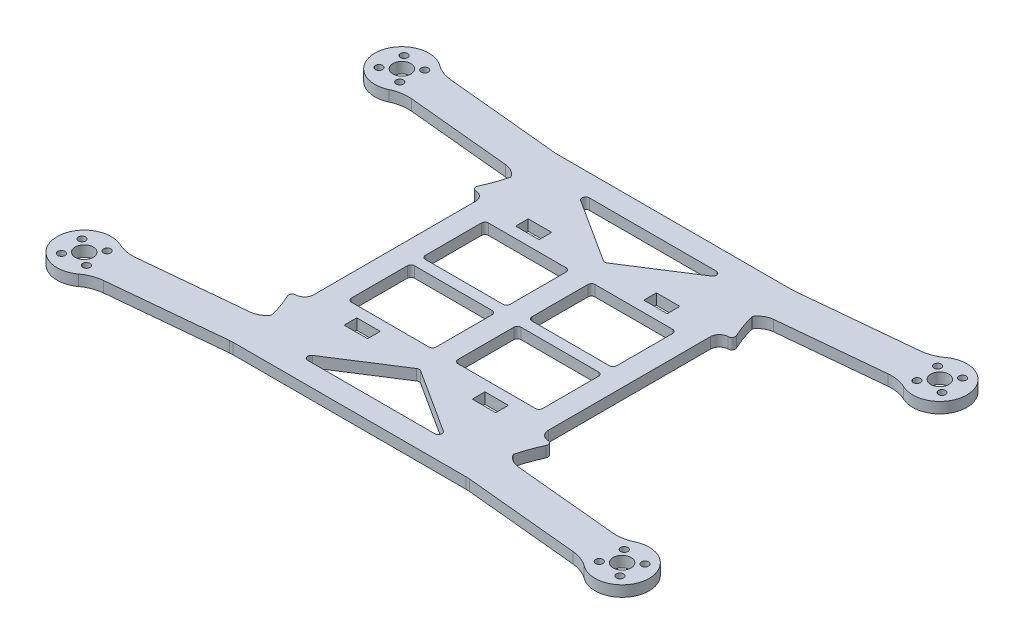
SolidWorks part; units mm, degrees
material "Custom PLA"
ref_plane "Front Plane" through (0, 0, 0) normal (0, 0, 1) x (1, 0, 0)
ref_plane "Top Plane" through (0, 0, 0) normal (0, 1, 0) x (1, 0, 0)
ref_plane "Right Plane" through (0, 0, 0) normal (1, 0, 0) x (0, 0, -1)
sketch "Sketch1" plane through (0, 0, 0) normal (0, 1, 0) x (1, 0, 0)
  line L0 (-101.3207, 0) -> (4964.7124, 0) construction
  line L1 (0, -101.3207) -> (0, 4964.7124) construction
  line L4 (33.2085, 45.046) -> (65.0466, 48.1117)
  line L5 (37.1258, 35.377) -> (66.0089, 38.1581)
  line L6 (0.5402, 25.8595) -> (18.1402, 37.1585)
  line L7 (4, 1.5) -> (25.5, 1.5)
  line L8 (3, 2.5) -> (3, 18)
  line L9 (4, 19) -> (25.5, 19)
  line L10 (26.5, 2.5) -> (26.5, 18)
  line L11 (14.5, 22) -> (21, 22)
  line L12 (14.5, 22) -> (14.5, 25.5)
  line L13 (14.5, 25.5) -> (21, 25.5)
  line L14 (21, 22) -> (21, 25.5)
  line L15 (17.6, 39) -> (-17.6, 39)
  line L16 (-18.1402, 37.1585) -> (-0.5402, 25.8595)
  line L17 (71.6376, 40.5277) -> (71.0277, 46.8624) construction
  line L18 (32.5, 22.4419) -> (32.5, -22.4419)
  line L30 (32.25, 45) -> (-32.25, 45)
  line L31 (-71.6376, 40.5277) -> (-71.0277, 46.8624) construction
  line L70 (-32.5, 22.4419) -> (-32.5, -22.4419)
  line L71 (-21, 22) -> (-21, 25.5)
  line L72 (-14.5, 25.5) -> (-21, 25.5)
  line L73 (-14.5, 22) -> (-14.5, 25.5)
  line L74 (-14.5, 22) -> (-21, 22)
  line L75 (-26.5, 2.5) -> (-26.5, 18)
  line L76 (-4, 19) -> (-25.5, 19)
  line L77 (-3, 2.5) -> (-3, 18)
  line L78 (-4, 1.5) -> (-25.5, 1.5)
  line L79 (-37.1258, 35.377) -> (-66.0089, 38.1581)
  line L80 (-33.2085, 45.046) -> (-65.0466, 48.1117)
  line L81 (-71.6376, -40.5277) -> (-71.0277, -46.8624) construction
  line L82 (71.6376, -40.5277) -> (71.0277, -46.8624) construction
  line L83 (-33.2085, -45.046) -> (-65.0466, -48.1117)
  line L84 (-37.1258, -35.377) -> (-66.0089, -38.1581)
  line L85 (-4, -1.5) -> (-25.5, -1.5)
  line L86 (-3, -2.5) -> (-3, -18)
  line L87 (-4, -19) -> (-25.5, -19)
  line L88 (-26.5, -2.5) -> (-26.5, -18)
  line L89 (-14.5, -22) -> (-21, -22)
  line L90 (-14.5, -22) -> (-14.5, -25.5)
  line L91 (-14.5, -25.5) -> (-21, -25.5)
  line L92 (-21, -22) -> (-21, -25.5)
  line L93 (32.25, -45) -> (-32.25, -45)
  line L94 (-18.1402, -37.1585) -> (-0.5402, -25.8595)
  line L95 (17.6, -39) -> (-17.6, -39)
  line L96 (21, -22) -> (21, -25.5)
  line L97 (14.5, -25.5) -> (21, -25.5)
  line L98 (14.5, -22) -> (14.5, -25.5)
  line L99 (14.5, -22) -> (21, -22)
  line L100 (26.5, -2.5) -> (26.5, -18)
  line L101 (4, -19) -> (25.5, -19)
  line L102 (3, -2.5) -> (3, -18)
  line L103 (4, -1.5) -> (25.5, -1.5)
  line L104 (0.5402, -25.8595) -> (18.1402, -37.1585)
  line L105 (37.1258, -35.377) -> (66.0089, -38.1581)
  line L106 (33.2085, -45.046) -> (65.0466, -48.1117)
  line L107 (67.0345, -43.2812) -> (81.9655, -44.7188) construction
  line L108 (73.7812, -51.4655) -> (75.2188, -36.5345) construction
  arc A3 (37.1258, 35.377) -> (33.4143, 33.1273) centre (37.605, 30.4) ccw
  arc A4 (71.2717, 37.2303) -> (66.0089, 38.1581) centre (66.9673, 28.2041) ccw
  arc A5 (65.0466, 48.1117) -> (70.0378, 50.0281) centre (64.0881, 58.0657) ccw
  arc A6 (71.2717, 37.2303) -> (70.0378, 50.0281) centre (74.5, 44) ccw
  arc A7 (-17.6, 39) -> (-18.1402, 37.1585) centre (-17.6, 38) ccw
  arc A8 (18.1402, 37.1585) -> (17.6, 39) centre (17.6, 38) ccw
  arc A9 (0.5402, 25.8595) -> (-0.5402, 25.8595) centre (0, 26.701) cw
  circle A10 centre (74.5, 44) radius 2.5
  circle A11 centre (71.0277, 46.8624) radius 1
  circle A12 centre (77.3624, 47.4723) radius 1
  circle A13 centre (77.9723, 41.1376) radius 1
  circle A14 centre (71.6376, 40.5277) radius 1
  arc A54 (32.25, 45) -> (33.2085, 45.046) centre (32.25, 55) ccw
  arc A98 (33.4143, 33.1273) -> (35.8354, 26.3563) centre (74.5, 44) ccw
  arc A99 (35.8354, 26.3563) -> (34.9469, 24.9414) centre (34.9257, 25.9411) cw
  arc A100 (34.9469, 24.9414) -> (32.5, 22.4419) centre (35, 22.4419) ccw
  arc A101 (-34.9469, 24.9414) -> (-32.5, 22.4419) centre (-35, 22.4419) cw
  arc A102 (-35.8354, 26.3563) -> (-34.9469, 24.9414) centre (-34.9257, 25.9411) ccw
  arc A103 (-33.4143, 33.1273) -> (-35.8354, 26.3563) centre (-74.5, 44) cw
  arc A104 (-32.25, 45) -> (-33.2085, 45.046) centre (-32.25, 55) cw
  circle A105 centre (-71.6376, 40.5277) radius 1
  circle A106 centre (-77.9723, 41.1376) radius 1
  circle A107 centre (-77.3624, 47.4723) radius 1
  circle A108 centre (-71.0277, 46.8624) radius 1
  circle A109 centre (-74.5, 44) radius 2.5
  arc A110 (-71.2717, 37.2303) -> (-70.0378, 50.0281) centre (-74.5, 44) cw
  arc A111 (-65.0466, 48.1117) -> (-70.0378, 50.0281) centre (-64.0881, 58.0657) cw
  arc A112 (-71.2717, 37.2303) -> (-66.0089, 38.1581) centre (-66.9673, 28.2041) cw
  arc A113 (-37.1258, 35.377) -> (-33.4143, 33.1273) centre (-37.605, 30.4) cw
  arc A114 (-37.1258, -35.377) -> (-33.4143, -33.1273) centre (-37.605, -30.4) ccw
  arc A115 (-71.2717, -37.2303) -> (-66.0089, -38.1581) centre (-66.9673, -28.2041) ccw
  arc A116 (-65.0466, -48.1117) -> (-70.0378, -50.0281) centre (-64.0881, -58.0657) ccw
  arc A117 (-71.2717, -37.2303) -> (-70.0378, -50.0281) centre (-74.5, -44) ccw
  circle A118 centre (-74.5, -44) radius 2.5
  circle A119 centre (-71.0277, -46.8624) radius 1
  circle A120 centre (-77.3624, -47.4723) radius 1
  circle A121 centre (-77.9723, -41.1376) radius 1
  circle A122 centre (-71.6376, -40.5277) radius 1
  arc A123 (-32.25, -45) -> (-33.2085, -45.046) centre (-32.25, -55) ccw
  arc A124 (-33.4143, -33.1273) -> (-35.8354, -26.3563) centre (-74.5, -44) ccw
  arc A125 (-35.8354, -26.3563) -> (-34.9469, -24.9414) centre (-34.9257, -25.9411) cw
  arc A126 (-34.9469, -24.9414) -> (-32.5, -22.4419) centre (-35, -22.4419) ccw
  arc A127 (34.9469, -24.9414) -> (32.5, -22.4419) centre (35, -22.4419) cw
  arc A128 (35.8354, -26.3563) -> (34.9469, -24.9414) centre (34.9257, -25.9411) ccw
  arc A129 (33.4143, -33.1273) -> (35.8354, -26.3563) centre (74.5, -44) cw
  arc A130 (32.25, -45) -> (33.2085, -45.046) centre (32.25, -55) cw
  circle A131 centre (71.6376, -40.5277) radius 1
  circle A132 centre (77.9723, -41.1376) radius 1
  circle A133 centre (77.3624, -47.4723) radius 1
  circle A134 centre (71.0277, -46.8624) radius 1
  circle A135 centre (74.5, -44) radius 2.5
  arc A136 (0.5402, -25.8595) -> (-0.5402, -25.8595) centre (0, -26.701) ccw
  arc A137 (18.1402, -37.1585) -> (17.6, -39) centre (17.6, -38) cw
  arc A138 (-17.6, -39) -> (-18.1402, -37.1585) centre (-17.6, -38) cw
  arc A139 (71.2717, -37.2303) -> (70.0378, -50.0281) centre (74.5, -44) cw
  arc A140 (65.0466, -48.1117) -> (70.0378, -50.0281) centre (64.0881, -58.0657) cw
  arc A141 (71.2717, -37.2303) -> (66.0089, -38.1581) centre (66.9673, -28.2041) cw
  arc A142 (37.1258, -35.377) -> (33.4143, -33.1273) centre (37.605, -30.4) cw
  arc A143 (25.5, 1.5) -> (26.5, 2.5) centre (25.5, 2.5) ccw
  arc A144 (25.5, 19) -> (26.5, 18) centre (25.5, 18) cw
  arc A145 (3, 18) -> (4, 19) centre (4, 18) cw
  arc A146 (4, 1.5) -> (3, 2.5) centre (4, 2.5) cw
  arc A147 (-3, 2.5) -> (-4, 1.5) centre (-4, 2.5) cw
  arc A148 (-4, 19) -> (-3, 18) centre (-4, 18) cw
  arc A149 (-26.5, 18) -> (-25.5, 19) centre (-25.5, 18) cw
  arc A150 (-26.5, 2.5) -> (-25.5, 1.5) centre (-25.5, 2.5) ccw
  arc A151 (3, -2.5) -> (4, -1.5) centre (4, -2.5) cw
  arc A152 (26.5, -2.5) -> (25.5, -1.5) centre (25.5, -2.5) ccw
  arc A153 (26.5, -18) -> (25.5, -19) centre (25.5, -18) cw
  arc A154 (4, -19) -> (3, -18) centre (4, -18) cw
  arc A155 (-25.5, -1.5) -> (-26.5, -2.5) centre (-25.5, -2.5) ccw
  arc A156 (-4, -1.5) -> (-3, -2.5) centre (-4, -2.5) cw
  arc A157 (-3, -18) -> (-4, -19) centre (-4, -18) cw
  arc A158 (-25.5, -19) -> (-26.5, -18) centre (-25.5, -18) cw
  point P37 (0, 25.5127)
  point P41 (0, 0)
  point P50 (74.5, 44)
  point P64 (32.5, 0)
  point P82 (0, 45)
  point P91 (-74.5, 44)
  point P164 (-32.5, 0)
  point P172 (-74.5, -44)
  point P173 (0, -45)
  point P174 (74.5, -44)
  point P175 (0, -25.5127)
  point P178 (26.5, 1.5)
  point P181 (26.5, 19)
  point P184 (3, 19)
  point P187 (3, 1.5)
  point P190 (-3, 1.5)
  point P193 (-3, 19)
  point P196 (-26.5, 19)
  point P199 (-26.5, 1.5)
  point P202 (3, -1.5)
  point P205 (26.5, -1.5)
  point P208 (26.5, -19)
  point P211 (3, -19)
  point P214 (-26.5, -1.5)
  point P217 (-3, -1.5)
  point P220 (-3, -19)
  point P223 (-26.5, -19)
  dimension "D5" = 42.5
  dimension "D6" = 5
  dimension "D7" = 10
  dimension "D8" = 7.5
  dimension "D9" = 149
  dimension "D10" = 88
  dimension "D16" = 14.5
  dimension "D18" = 1
  dimension "D30" = 5
  dimension "D11" = 10
  dimension "D22" = 6
  dimension "D33" = 1
  dimension "D29" = 2.5
  dimension "D34" = 1
  dimension "D35" = 2
  dimension "D4" = 174.5
  dimension "D12" = 32.5
  dimension "D13" = 10
  dimension "D14" = 64.5
  dimension "D15" = 6.5
  dimension "D17" = 3
  dimension "D19" = 35.2
  dimension "D20" = 32.7
  dimension "D21" = 23.5
  dimension "D23" = 6
  dimension "D24" = 1.5
  dimension "D25" = 45
  dimension "D26" = 30.4
  dimension "D27" = 3.5
  dimension "D28" = 22
  dimension "D31" = 4.5
  dimension "D32" = 4
extrude "Boss-Extrude1" add sketch "Sketch1" along normal mid plane 3
